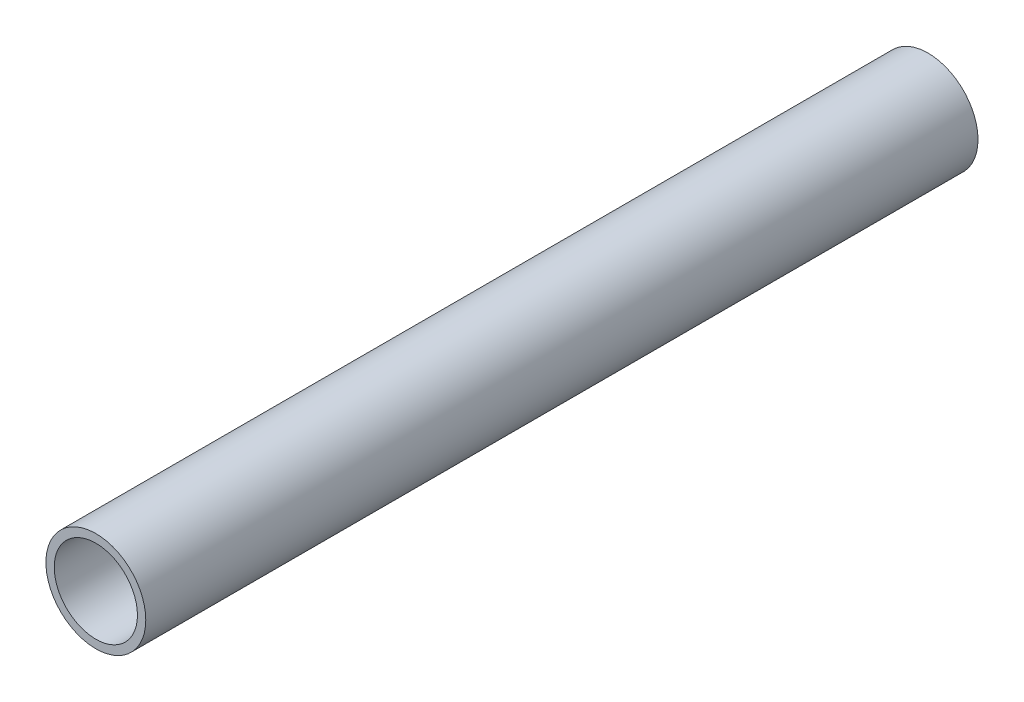
SolidWorks part; units mm, degrees
ref_plane "Ebene vorne" through (0, 0, 0) normal (0, 0, 1) x (1, 0, 0)
ref_plane "Ebene oben" through (0, 0, 0) normal (0, 1, 0) x (1, 0, 0)
ref_plane "Ebene rechts" through (0, 0, 0) normal (1, 0, 0) x (0, 0, -1)
sketch "Sketch1" plane through (0, 0, 0) normal (0, 0, 1) x (1, 0, 0)
  circle A0 centre (0, 0) radius 3
  circle A1 centre (0, 0) radius 2.5
  dimension "D1" = 6
  dimension "D2" = 5
extrude "Boss-Extrude1" add sketch "Sketch1" along normal blind 50
